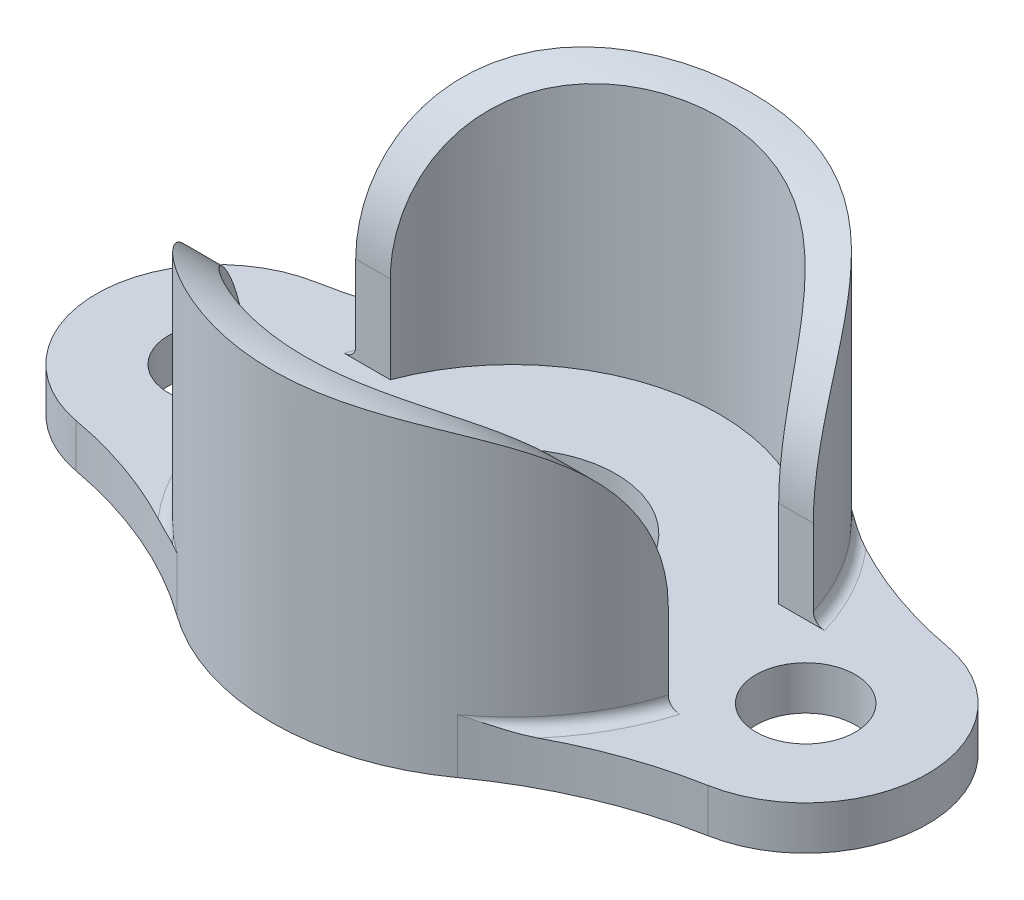
SolidWorks part; units mm, degrees
ref_plane "Front Plane" through (0, 0, 0) normal (0, 0, 1) x (1, 0, 0)
ref_plane "Top Plane" through (0, 0, 0) normal (0, 1, 0) x (1, 0, 0)
ref_plane "Right Plane" through (0, 0, 0) normal (1, 0, 0) x (0, 0, -1)
sketch "Sketch3" plane through (0, 0, 0) normal (0, 1, 0) x (1, 0, 0)
  line L0 (0, 5.5) -> (0, -5.5) construction
  arc A0 (-5.032, -2.2201) -> (5.032, -2.2201) centre (0, 0) ccw
  circle A1 centre (6.73, 0) radius 1.14
  circle A2 centre (-6.73, 0) radius 1.14
  arc A3 (-5.032, 2.2201) -> (-5.032, -2.2201) centre (-6.73, 0) ccw
  arc A4 (5.032, 2.2201) -> (5.032, -2.2201) centre (6.73, 0) cw
  arc A5 (5.032, 2.2201) -> (-5.032, 2.2201) centre (0, 0) ccw
  dimension "D1" = 11
  dimension "D2" = 2.28
  dimension "D6" = 5.59
  dimension "D3" = 6.73
  dimension "D4" = 13.46
extrude "Boss-Extrude2" add sketch "Sketch3" along normal blind 1
fillet "Fillet2" radius 10 4 edges at (-5.032, 0.5, -2.2201) (5.032, 0.5, -2.2201) (5.032, 0.5, 2.2201) (-5.032, 0.5, 2.2201)
sketch "Sketch4" plane through (0, 1, 0) normal (0, 1, 0) x (1, 0, 0)
  line L0 (4.45, -1.6613) -> (5.2431, -1.6613)
  line L1 (-5.2431, -1.6613) -> (-4.45, -1.6613)
  line L2 (4.45, 1.6613) -> (5.2431, 1.6613)
  line L3 (-5.2431, 1.6613) -> (-4.45, 1.6613)
  line L5 (-5.2431, -1.6613) -> (5.2431, 1.6613) construction
  line L6 (-5.2431, 1.6613) -> (5.2431, -1.6613) construction
  arc A0 (-5.2431, -1.6613) -> (5.2431, -1.6613) centre (0, 0) ccw
  arc A1 (-4.45, -1.6613) -> (4.45, -1.6613) centre (0, 0) ccw
  arc A2 (4.45, 1.6613) -> (-4.45, 1.6613) centre (0, 0) ccw
  circle A3 centre (0, 0) radius 5.5 construction
  circle A4 centre (0, 0) radius 4.75 construction
  arc A5 (5.2431, 1.6613) -> (-5.2431, 1.6613) centre (0, 0) ccw
  point P1 (4.5424, 1.3888)
  point P9 (5.2597, 1.608)
  dimension "D1" = 11
  dimension "D3" = 3.3225
  dimension "D2" = 0.75
extrude "Boss-Extrude6" add sketch "Sketch4" along normal blind 6
fillet "Fillet6" radius 4 2 edges at (-4.8466, 7, 1.6613) (-4.8466, 7, -1.6613)
fillet "Fillet4" radius 0.25 4 edges at (-4.4538, 1, 3.227) (4.4538, 1, 3.227)
sketch "Sketch6" plane through (0, 1, 0) normal (0, 1, 0) x (1, 0, 0)
  circle A0 centre (0, 0) radius 2.38
  dimension "D1" = 4.76
extrude "Cut-Extrude1" cut sketch "Sketch6" against normal blind 5
equation "\"e\"=4"
